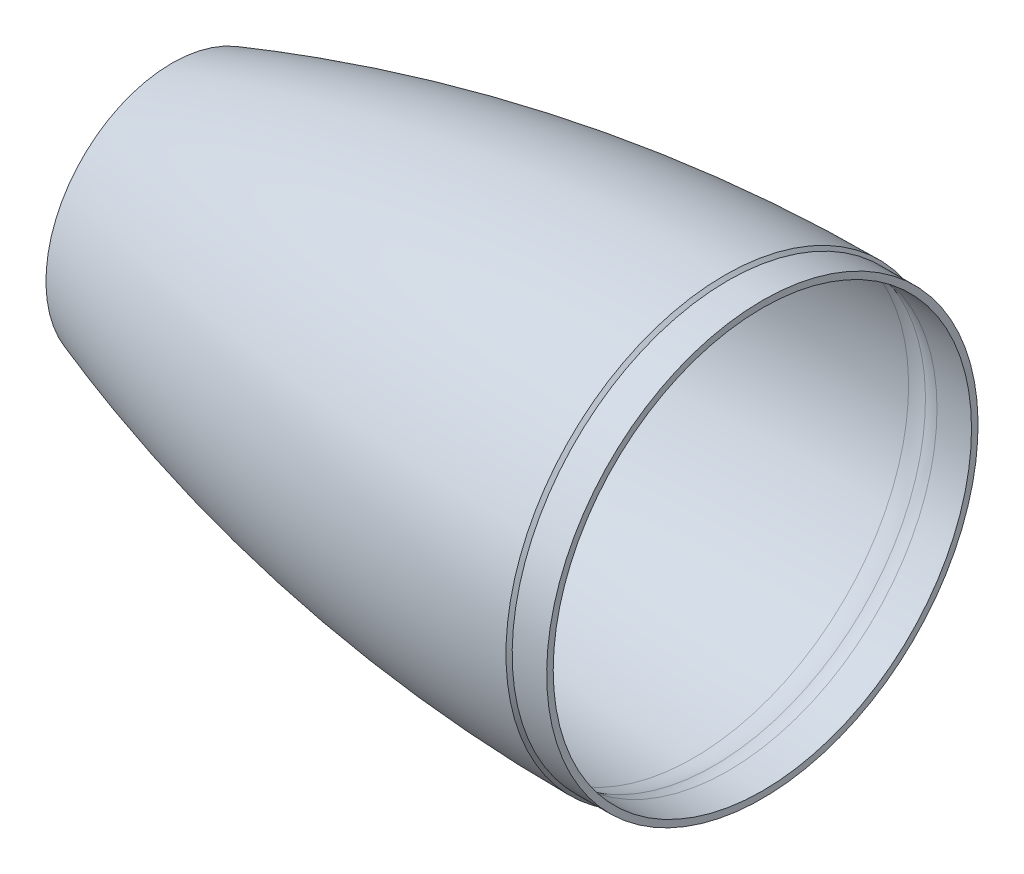
SolidWorks part; units mm, degrees
ref_plane "Front Plane" through (0, 0, 0) normal (0, 0, 1) x (1, 0, 0)
ref_plane "Top Plane" through (0, 0, 0) normal (0, 1, 0) x (1, 0, 0)
ref_plane "Right Plane" through (0, 0, 0) normal (1, 0, 0) x (0, 0, -1)
sketch "Sketch1" plane through (0, 0, 0) normal (0, 0, 1) x (1, 0, 0)
  line L4 (0, 0) -> (-304.8, 0) construction
  line L9 (0, 76.975) -> (0, 0) construction
  line L10 (0, 80.518) -> (50.8, 80.518) construction
  line L15 (1.143, 79.375) -> (13.843, 79.375)
  line L16 (0, 80.518) -> (1.143, 79.375)
  line L17 (1.143, 76.975) -> (13.843, 76.975)
  line L18 (13.843, 76.975) -> (13.843, 79.375)
  line L19 (-203.454, 46.355) -> (-203.454, 44.1325)
  line L20 (-203.454, 44.1325) -> (-199.644, 44.1325)
  line L21 (-199.644, 44.1325) -> (-195.834, 47.6691)
  arc A4 (0, 80.518) -> (-203.454, 46.355) centre (0, -542.3875) ccw
  arc A5 (-11.557, 79.2106) -> (-195.834, 47.6691) centre (0, -542.3875) ccw
  arc A6 (0, 79.318) -> (-203.0621, 45.2208) centre (0, -542.3875) ccw construction
  arc A10 (-4.0446, 77.9176) -> (1.143, 76.975) centre (1.143, 91.7214) ccw
  arc A13 (-11.557, 79.2106) -> (-4.0446, 77.9176) centre (-11.18, 58.9308) cw
  point P8 (-57.2734, -19.8104)
  point P9 (0, 313.4439)
  point P10 (-150.9565, 274.6984)
  dimension "D7" = 3.81
  dimension "D17" = 5.1876
  dimension "D8" = 3.81
  dimension "D16" = 12.7
  dimension "D1" = 161.036
  dimension "D2" = 50.8
  dimension "D3" = 203.454
  dimension "D4" = 92.71
  dimension "D6" = 88.265
  dimension "D9" = 304.8
  dimension "D12" = 12.7
  dimension "D13" = 158.75
  dimension "D14" = 45
  dimension "D15" = 2.4
  dimension "D5" = 1.2
revolve "Revolve1" add sketch "Sketch1" angle 360 about L4
fillet "Fillet1" radius 3.175 2 edges at (-199.644, 44.1325, 0) (-195.834, 47.6691, 0)
